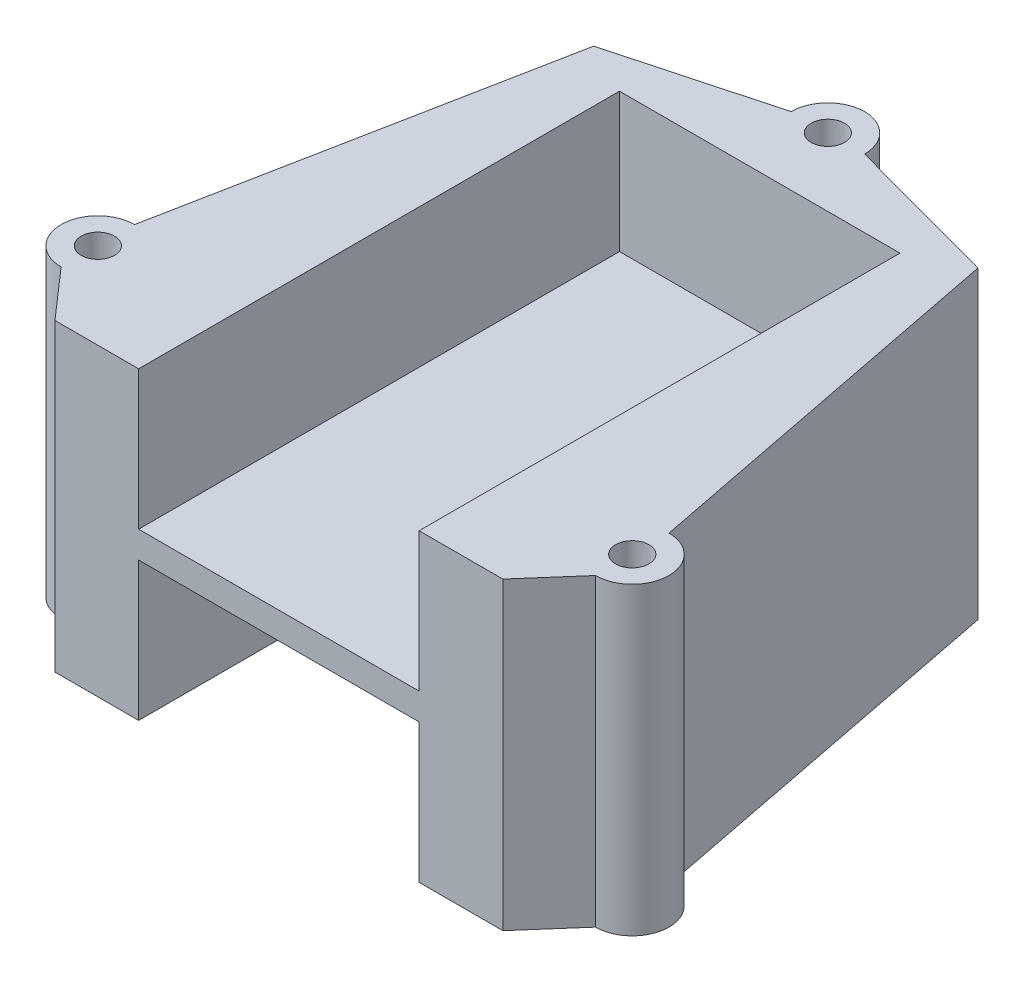
SolidWorks part; units mm, degrees
material "PLA"
ref_plane "Front Plane" through (0, 0, 0) normal (0, 0, 1) x (1, 0, 0)
ref_plane "Top Plane" through (0, 0, 0) normal (0, 1, 0) x (1, 0, 0)
ref_plane "Right Plane" through (0, 0, 0) normal (1, 0, 0) x (0, 0, -1)
sketch "Sketch1" plane through (0, 0, 0) normal (0, 1, 0) x (1, 0, 0)
  line L0 (0, 0) -> (0, 38.1)
  circle A0 centre (0, 0) radius 38.1
  circle A2 centre (0, 29.337) radius 1.5875
  circle A3 centre (25.4066, -14.6685) radius 1.5875
  circle A4 centre (-25.4066, -14.6685) radius 1.5875
  point P12 (0, 0)
  dimension "D1" = 3.175
  dimension "D3" = 76.2
  dimension "D2" = 8.763
  dimension "D4" = 3
extrude "Boss-Extrude1" add sketch "Sketch1" along normal blind 2.54 contours A2 A0 A4 A3 region at (26.1788, 0, -26.1788)
sketch "Sketch2" plane through (0, 2.54, 0) normal (0, 1, 0) x (1, 0, 0)
  line L1 (13.335, 2.54) -> (0, 2.54) construction
  line L14 (13.335, -20.32) -> (-13.335, -20.32)
  line L15 (13.335, -20.32) -> (13.335, 25.4)
  line L16 (13.335, 25.4) -> (-13.335, 25.4)
  line L17 (-13.335, -20.32) -> (-13.335, 25.4)
  line L18 (0, 38.1) -> (0, -38.1) construction
  line L19 (0, 2.54) -> (-13.335, 2.54) construction
  line L20 (25.4066, -11.176) -> (18.2707, 25.3425)
  line L21 (25.4066, -18.161) -> (21.2951, -22.86)
  line L22 (18.2707, 25.3425) -> (3.4925, 29.337)
  line L23 (21.2951, -22.86) -> (-21.2951, -22.86)
  line L24 (-18.2707, 25.3425) -> (-3.4925, 29.337)
  line L25 (-25.4066, -11.176) -> (-18.2707, 25.3425)
  line L26 (-25.4066, -18.161) -> (-21.2951, -22.86)
  circle A20 centre (0, 0) radius 29.337 construction
  circle A22 centre (0, 0) radius 38.1 construction
  circle A51 centre (0, 0) radius 31.242 construction
  circle A52 centre (25.4066, -14.6685) radius 3.4925
  circle A53 centre (25.4066, -14.6685) radius 3.4925
  circle A55 centre (-25.4066, -14.6685) radius 3.4925
  circle A56 centre (0, 29.337) radius 3.4925
  circle A57 centre (0, 29.337) radius 3.4925
  point P20 (10.8816, 27.3397)
  point P25 (-10.8816, 27.3397)
  point P36 (0, -22.86)
  circle M4 centre (0, 29.337) radius 1.5875
  circle M6 centre (-25.4066, -14.6685) radius 1.5875
  circle M7 centre (25.4066, -14.6685) radius 1.5875
  dimension "D5" = 1.905
  dimension "D7" = 2.54
  dimension "D8" = 116.182
  dimension "D1" = 26.67
  dimension "D2" = 45.72
  dimension "D3" = 25.4
  dimension "D4" = 1.905
  dimension "D6" = 1.905
extrude "Boss-Extrude2" add sketch "Sketch2" along normal blind 28.956 separate body contours A57 L24 L25 A55 L26 L23 L21 A53 L20 L22 L14 L17 L16 L15 | L17 L14 L15 L16 | A55 M6 | A53 M7 | A57 M4 region at (0, 2.54, -2.54) region at (21.1856, 2.54, 14.6685) region at (27.8063, 2.54, 12.2688) region at (0, 2.54, -25.9433) region at (-28.8003, 2.54, 14.6685)
delete or keep bodies "Body-Delete/Keep 1" type delete bodies bodies 101
sketch "Sketch3" plane through (0, 0, 22.86) normal (0, 0, 1) x (1, 0, 0)
  line L0 (0, 31.496) -> (0, 2.54) construction
  line L1 (13.335, 36.068) -> (-13.335, 36.068)
  line L2 (13.335, 36.068) -> (13.335, 18.288)
  line L3 (13.335, 18.288) -> (-13.335, 18.288)
  line L4 (-13.335, 36.068) -> (-13.335, 18.288)
  line L5 (21.2951, 31.496) -> (-21.2951, 31.496) construction
  line L6 (21.2951, 2.54) -> (-21.2951, 2.54) construction
  line L7 (13.335, 36.068) -> (21.2951, 36.068) construction
  line L8 (21.2951, 31.496) -> (21.2951, 2.54) construction
  line L9 (21.2951, 17.018) -> (-18.387, 17.018) construction
  line L11 (-13.335, -2.032) -> (-13.335, 15.748)
  line L12 (-13.335, 36.068) -> (-21.2951, 36.068) construction
  line L13 (-21.2951, 31.496) -> (-21.2951, 2.54) construction
  line L14 (13.335, 15.748) -> (-13.335, 15.748)
  line L15 (13.335, -2.032) -> (13.335, 15.748)
  line L16 (13.335, -2.032) -> (-13.335, -2.032)
  dimension "D1" = 17.78
  dimension "D2" = 26.67
  dimension "D3" = 1.27
extrude "Cut-Extrude1" cut sketch "Sketch3" against normal blind 45.72
ref_plane "Fastner Plane" through (0, 0, 12.7) normal (0, 0, 1) x (1, 0, 0)
